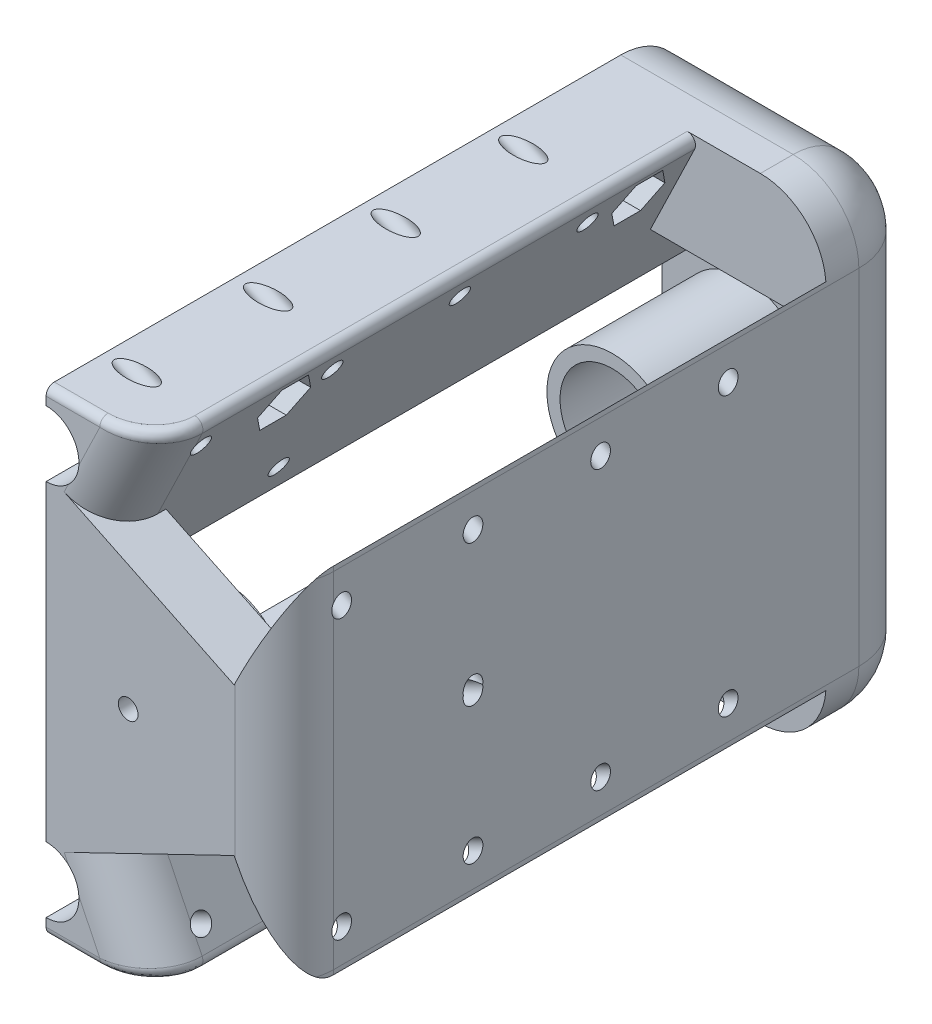
SolidWorks part; units mm, degrees
ref_plane "前视基准面" through (0, 0, 0) normal (0, 0, 1) x (1, 0, 0)
ref_plane "上视基准面" through (0, 0, 0) normal (0, 1, 0) x (1, 0, 0)
ref_plane "右视基准面" through (0, 0, 0) normal (1, 0, 0) x (0, 0, -1)
sketch "草图1" plane through (0, 0, 0) normal (0, 0, 1) x (1, 0, 0)
  line L1 (0, 0) -> (14.5, 0)
  line L2 (0, 0) -> (0, -29)
  line L3 (0, -29) -> (14.5, -29)
  line L4 (14.5, 0) -> (14.5, -29)
  dimension "D1" = 29
  dimension "D2" = 14.5
extrude "凸台-拉伸1" add sketch "草图1" along normal blind 39
sketch "草图2" plane through (0, 0, 39) normal (0, 0, 1) x (1, 0, 0)
  line L0 (6.8475, 0) -> (3.8005, -6.302)
  line L1 (14.5, 0) -> (0, 0) construction
  line L2 (3.8005, -6.302) -> (11.4529, -10.002)
  line L3 (11.4529, -10.002) -> (14.5, -3.7)
  line L4 (14.5, -29) -> (14.5, 0) construction
  line L5 (14.5, -25.3) -> (11.4529, -18.998)
  line L6 (11.4529, -18.998) -> (3.8005, -22.698)
  line L7 (3.8005, -22.698) -> (6.8475, -29)
  line L8 (0, -29) -> (14.5, -29) construction
  line L9 (14.5, -3.7) -> (14.5, 0)
  line L13 (0, 0) -> (0, -29)
  line L14 (0, -29) -> (14.5, -29)
  line L15 (14.5, -29) -> (14.5, 0)
  line L16 (14.5, 0) -> (0, 0)
  line L18 (6.8475, -29) -> (14.5, -29)
  line L19 (14.5, -29) -> (14.5, -25.3)
  line L20 (14.5, 0) -> (6.8475, 0)
  dimension "D1" = 8.5
  dimension "D2" = 8.5
  dimension "D3" = 3.7
  dimension "D4" = 7
  dimension "D5" = 0
extrude "履带槽" cut sketch "草图2" against normal blind 33
sketch "草图6" plane through (0, 0, 39) normal (0, 0, 1) x (1, 0, 0)
  line L0 (3.8005, -22.698) -> (0, -22.698)
  line L1 (0, 0) -> (0, -29) construction
sketch "草图3" plane through (0, 0, 0) normal (-1, 0, 0) x (0, 0, 1)
  line L0 (0, 0) -> (0, -29) construction
  line L1 (1.5, -6.302) -> (37.5, -6.302)
  line L2 (1.5, -6.302) -> (1.5, -22.698)
  line L3 (1.5, -22.698) -> (37.5, -22.698)
  line L4 (37.5, -6.302) -> (37.5, -22.698)
  line L5 (39, 0) -> (0, 0) construction
  point P4 (1.5, -14.5)
  point P7 (0, -14.5)
  point P8 (19.5, -6.302)
  point P11 (19.5, 0)
  dimension "D1" = 36
extrude "切除-拉伸2" cut sketch "草图3" against normal blind 12
sketch "草图4" plane through (0, 0, 39) normal (0, 0, 1) x (1, 0, 0)
  line L0 (14.5, -25.3) -> (14.5, -3.7) construction
  circle A0 centre (5, -14.5) radius 0.6
  point P6 (14.5, -14.5)
  dimension "D1" = 1.2
  dimension "D2" = 9.5
extrude "电机轴" cut sketch "草图4" against normal up to next
sketch "草图5" plane through (0, 0, 39) normal (0, 0, 1) x (1, 0, 0)
  line L0 (6.8475, -29) -> (3.8005, -22.698)
  line L1 (3.8005, -22.698) -> (1.7707, -18.5)
  line L2 (1.7707, -18.5) -> (0, -18.5)
  line L3 (0, 0) -> (0, -29) construction
  line L4 (6.8475, 0) -> (3.8005, -6.302)
  line L5 (3.8005, -6.302) -> (1.7707, -10.5)
  line L6 (1.7707, -10.5) -> (0, -10.5)
  line L7 (0, 0) -> (0, -10.5)
  line L8 (0, -29) -> (6.8475, -29) construction
  line L9 (0, -29) -> (6.8475, -29)
  line L10 (6.8475, 0) -> (0, 0) construction
  line L11 (6.8475, 0) -> (0, 0)
  line L12 (0, -18.5) -> (0, -29)
  dimension "D1" = 8
extrude "凸台-拉伸2" add sketch "草图5" against normal up to next
sketch "草图7" plane through (-5.8147, -2.8115, 0) normal (0.9003, 0.4353, 0) x (0, 0, -1)
  circle A0 centre (-35.5, -26.9891) radius 0.6
  circle A1 centre (-27.5, -26.9891) radius 0.6
  circle A2 centre (-19.73, -26.9891) radius 0.6
  circle A3 centre (-11.96, -26.9891) radius 0.6
  circle A4 centre (-27.5, -19.4891) radius 0.6
  dimension "D1" = 1.2
  dimension "D2" = 1.2
  dimension "D3" = 1.2
  dimension "D4" = 1.2
  dimension "D5" = 1.2
  dimension "D6" = 8
  dimension "D7" = 7.77
  dimension "D8" = 7.77
  dimension "D9" = 7.5
  dimension "D10" = 9.6
  dimension "D11" = 11.5
extrude "齿轮轴" cut sketch "草图7" against normal through all both and the other way through all
ref_plane "基准面1" through (0, -14.5, 0) normal (0, 1, 0) x (1, 0, 0)
mirror "镜向1" about plane through (0, -14.5, 0) normal (0, 1, 0) of "齿轮轴"
sketch "草图8" plane through (0, 0, 1.5) normal (0, 0, 1) x (1, 0, 0)
  circle A0 centre (5, -14.5) radius 3.2
  circle A1 centre (5, -14.5) radius 4
  dimension "D1" = 6.4
  dimension "D2" = 8
extrude "凸台-拉伸3" add sketch "草图8" along normal blind 8
sketch "草图9" plane through (0, 0, 1.5) normal (0, 0, 1) x (1, 0, 0)
  line L0 (5.5, -11.3393) -> (5.5, -13.0858)
  line L1 (4.5, -11.3393) -> (4.5, -13.0858)
  line L2 (5.5, -15.9142) -> (5.5, -17.6607)
  line L3 (4.5, -15.9142) -> (4.5, -17.6607)
  arc A0 (4.5, -13.0858) -> (4.5, -15.9142) centre (5, -14.5) ccw
  circle A1 centre (5, -14.5) radius 3.2 construction
  arc A2 (4.5, -17.6607) -> (5.5, -17.6607) centre (5, -14.5) ccw
  arc A3 (5.5, -15.9142) -> (5.5, -13.0858) centre (5, -14.5) ccw
  arc A4 (5.5, -11.3393) -> (4.5, -11.3393) centre (5, -14.5) ccw
  dimension "D1" = 3
  dimension "D2" = 1
extrude "切除-拉伸5" cut sketch "草图9" against normal through all
sketch "草图11" plane through (0, 0, 37.5) normal (0, 0, -1) x (-1, 0, 0)
  circle A0 centre (-5, -14.5) radius 3.15
  circle A1 centre (-5, -14.5) radius 3.65
  dimension "D1" = 6.3
  dimension "D2" = 7.3
extrude "凸台-拉伸4" add sketch "草图11" along normal blind 4.5
fillet "圆角1" radius 4 2 edges at (14.5, 0, 3) (14.5, -29, 3) tangent propagation no
fillet "圆角2" radius 4 5 edges at (5.25, -29, 0) (13.3284, -27.8284, 0) (5.25, 0, 0) (13.3284, -1.1716, 0) (14.5, -14.5, 0)
fillet "圆角3" radius 3 3 edges at (14.5, -14.5, 39) (14.4976, -25.14, 39) (14.4976, -3.86, 39)
fillet "圆角4" radius 3 2 edges at (5.324, -25.849, 39) (5.324, -3.151, 39)
sketch "草图14" plane through (0, 0, 37.5) normal (0, 0, -1) x (-1, 0, 0)
  line L6 (-1.3243, -10.5) -> (-3.4386, -6.1271)
  line L8 (-1.3243, -10.5) -> (-3.4386, -6.1271)
  line L10 (0, -18.5) -> (0, -10.5)
  line L11 (0, -10.5) -> (-1.3243, -10.5)
  line L15 (-12, -8.8706) -> (-12, -20.1294)
  line L17 (-3.4386, -6.1271) -> (-11.4529, -10.002)
  line L19 (-1.3243, -18.5) -> (0, -18.5)
  line L20 (0, -18.5) -> (0, -10.5)
  line L21 (0, -10.5) -> (-1.3243, -10.5)
  line L25 (-12, -8.8706) -> (-12, -20.1294)
  line L29 (-1.3243, -18.5) -> (0, -18.5)
  line L32 (-3.4386, -6.1271) -> (-11.4529, -10.002)
  line L34 (-11.4529, -10.002) -> (-12, -8.8706)
  line L35 (-11.4529, -10.002) -> (-12, -8.8706)
  line L36 (-12, -20.1294) -> (-11.4529, -18.998)
  line L37 (-12, -20.1294) -> (-11.4529, -18.998)
  line L38 (-11.4529, -18.998) -> (-3.4386, -22.8729)
  line L39 (-11.4529, -18.998) -> (-3.4386, -22.8729)
  line L40 (-3.4386, -22.8729) -> (-1.3243, -18.5)
  line L41 (-3.4386, -22.8729) -> (-1.3243, -18.5)
  dimension "D1" = 0
extrude "凸台-拉伸5" add sketch "草图14" along normal blind 2
ref_plane "基准面2" through (3.5, 0, 0) normal (-1, 0, 0) x (0, 0, 1)
sketch "草图16" plane through (3.5, 0, 0) normal (-1, 0, 0) x (0, 0, 1)
  line L0 (29.3834, -1) -> (28.5751, -2.4)
  line L1 (28.5751, -2.4) -> (29.3834, -3.8)
  line L2 (29.3834, -3.8) -> (31, -3.8)
  line L3 (31, -3.8) -> (31.8083, -2.4)
  line L4 (31.8083, -2.4) -> (31, -1)
  line L5 (31, -1) -> (29.3834, -1)
  line L6 (39, -19.0953) -> (39, -9.9047) construction
  line L7 (9.4249, -1) -> (7.8083, -1)
  line L8 (7.8083, -1) -> (7, -2.4)
  line L9 (7, -2.4) -> (7.8083, -3.8)
  line L10 (7.8083, -3.8) -> (9.4249, -3.8)
  line L11 (9.4249, -3.8) -> (10.2332, -2.4)
  line L12 (10.2332, -2.4) -> (9.4249, -1)
  dimension "D1" = 2.8
  dimension "D2" = 120
  dimension "D3" = 120
  dimension "D4" = 8
  dimension "D5" = 1
  dimension "D6" = 2.8
  dimension "D7" = 120
  dimension "D8" = 120
  dimension "D9" = 120
  dimension "D10" = 1
  dimension "D11" = 7
extrude "螺丝孔" cut sketch "草图16" against normal up to next
sketch "草图17" plane through (3.5, 0, 0) normal (1, 0, 0) x (0, 0, -1)
  line L1 (-9.4249, -1) -> (-7.8083, -1) construction
  line L3 (-29.3834, -1) -> (-31, -1) construction
  circle A0 centre (-30.1917, -2.4) radius 0.7
  circle A1 centre (-8.6166, -2.4) radius 0.7
  point P11 (-8.6166, -1)
  point P13 (-30.1917, -1)
  dimension "D1" = 1.4
  dimension "D2" = 1.4
extrude "切除-拉伸9" cut sketch "草图17" against normal through all
mirror "镜向2" about plane through (0, -14.5, 0) normal (0, 1, 0) of "切除-拉伸9", "螺丝孔"
sketch "草图18" plane through (0, 0, 35.5) normal (0, 0, -1) x (-1, 0, 0)
  circle A0 centre (-5, -14.5) radius 3.15 construction
  circle A1 centre (-5, -14.5) radius 3.15
extrude "凸台-拉伸6" [suppressed] add sketch "草图18" along normal blind 1.54
sketch "草图19" plane through (0, 0, 39) normal (0, 0, 1) x (1, 0, 0)
  circle A0 centre (5, -14.5) radius 0.6 construction
  circle A1 centre (5, -14.5) radius 0.6
extrude "切除-拉伸10" cut sketch "草图19" against normal up to next
sketch "草图20" [suppressed] plane through (0, 0, 39) normal (0, 0, 1) x (1, 0, 0)
  line L0 (0.3496, -21.4785) -> (8.8109, -17.3875)
  line L1 (-0.2612, -21.7739) -> (2.6687, -20.3572) construction
  line L2 (5, -14.5) -> (6.8537, -18.3338)
sketch "草图21" plane through (0, 0, 35.5) normal (0, 0, -1) x (-1, 0, 0)
  circle A0 centre (-5, -14.5) radius 3.15 construction
  circle A1 centre (-5, -14.5) radius 3.15
extrude "切除-拉伸11" cut sketch "草图21" against normal blind 0.46
sketch "草图12" plane through (0, 0, 39) normal (0, 0, 1) x (1, 0, 0)
  line L0 (0, 0) -> (0, -29) construction
  circle A0 centre (0, -26) radius 2
  circle A1 centre (0, -3) radius 2
  dimension "D1" = 4
  dimension "D2" = 4
  dimension "D3" = 3
  dimension "D4" = 3
extrude "CMOS" cut sketch "草图12" against normal through all
sketch "草图22" [suppressed] plane through (0, 0, 39) normal (0, 0, 1) x (1, 0, 0)
  line L0 (0, -0.5) -> (0, -1)
  line L1 (0, -23.5) -> (0, -24)
  line L2 (0, -5) -> (0, -5.5)
  line L3 (0, -28) -> (0, -28.5)
  arc A0 (0, -28) -> (1.8862, -26.6649) centre (0, -26) ccw construction
  arc A1 (1.8862, -26.6649) -> (0.6503, -24.1087) centre (0, -26) ccw construction
  arc A2 (0.6503, -24.1087) -> (0, -24) centre (0, -26) ccw construction
  arc A3 (0, -5) -> (0.6503, -4.8913) centre (0, -3) ccw construction
  arc A4 (0.6503, -4.8913) -> (1.8862, -2.3351) centre (0, -3) ccw construction
  arc A5 (1.8862, -2.3351) -> (0, -1) centre (0, -3) ccw construction
  arc A6 (0, -28) -> (1.8862, -26.6649) centre (0, -26) ccw
  arc A7 (1.8862, -26.6649) -> (0.6503, -24.1087) centre (0, -26) ccw
  arc A8 (0.6503, -24.1087) -> (0, -24) centre (0, -26) ccw
  arc A9 (0, -5) -> (0.6503, -4.8913) centre (0, -3) ccw
  arc A10 (0.6503, -4.8913) -> (1.8862, -2.3351) centre (0, -3) ccw
  arc A11 (1.8862, -2.3351) -> (0, -1) centre (0, -3) ccw
  arc A12 (0, -5.5) -> (0, -0.5) centre (0, -3) ccw
  arc A13 (0, -28.5) -> (0, -23.5) centre (0, -26) ccw
  dimension "D1" = 5
  dimension "D2" = 5
extrude "凸台-拉伸7" [suppressed] add sketch "草图22" along normal blind 0.5
fillet "圆角5" radius 0.5 6 edges at (6.8475, -29, 21) (5.8716, -29, 38.1213) (6.8475, 0, 21) (5.8716, 0, 38.1213) (1.7576, -29, 39) (1.7576, 0, 39)
